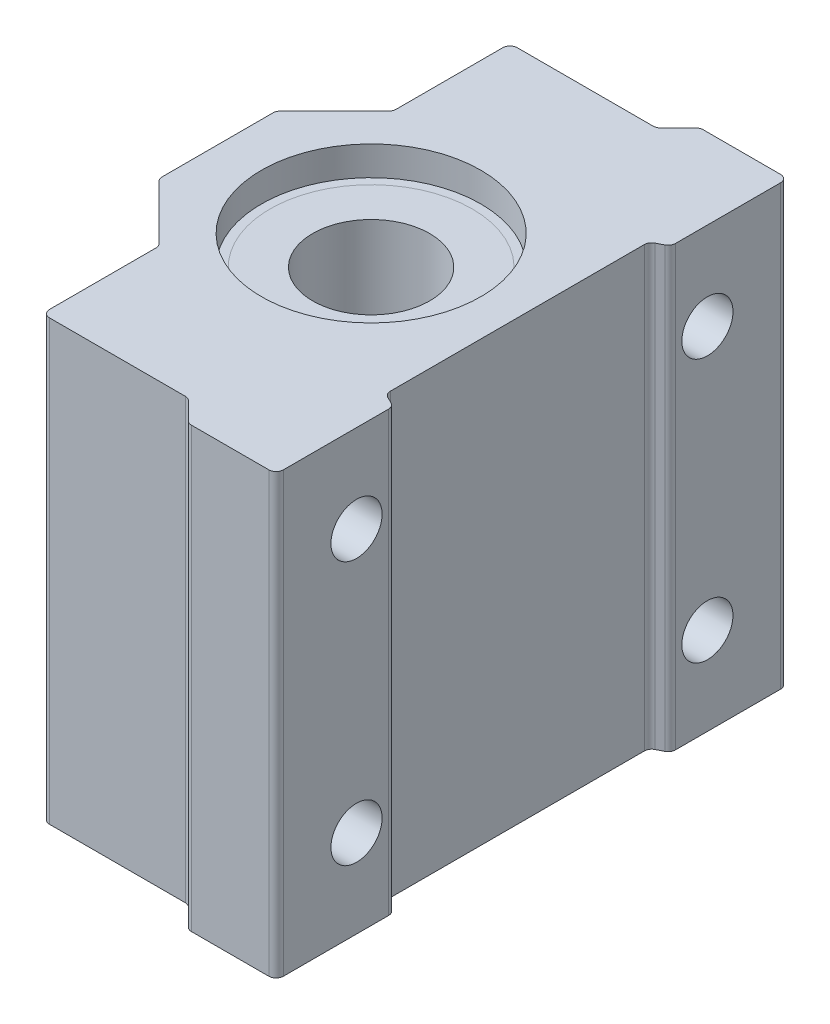
SolidWorks part; units mm, degrees
ref_plane "Front Plane" through (0, 0, 0) normal (0, 0, 1) x (1, 0, 0)
ref_plane "Top Plane" through (0, 0, 0) normal (0, 1, 0) x (1, 0, 0)
ref_plane "Right Plane" through (0, 0, 0) normal (1, 0, 0) x (0, 0, -1)
sketch "Sketch1" plane through (0, 0, 0) normal (0, 1, 0) x (1, 0, 0)
  line L0 (-2.4565, 16.1957) -> (3.5435, 16.1957)
  line L1 (-2.4565, 16.1957) -> (-2.4565, 14.6957) construction
  line L2 (-2.4565, 14.6957) -> (-3.9565, 14.6957) construction
  line L3 (-3.9565, 14.6957) -> (-2.4565, 16.1957)
  line L4 (-3.9565, 14.6957) -> (-13.9565, 14.6957)
  line L5 (-13.9565, 14.6957) -> (-13.9565, 6.6957)
  line L6 (-13.9565, 6.6957) -> (-17.9565, 6.6957) construction
  line L7 (-17.9565, 6.6957) -> (-17.9565, 2.6957) construction
  line L8 (-13.9565, 6.6957) -> (-17.9565, 2.6957)
  line L9 (-17.9565, 2.6957) -> (-17.9565, -5.3043)
  line L10 (-17.9565, -5.3043) -> (-17.9565, -9.3043) construction
  line L11 (-17.9565, -9.3043) -> (-13.9565, -9.3043) construction
  line L12 (-17.9565, -5.3043) -> (-13.9565, -9.3043)
  line L13 (-13.9565, -9.3043) -> (-13.9565, -17.3043)
  line L14 (-13.9565, -17.3043) -> (-3.9565, -17.3043)
  line L15 (-3.9565, -17.3043) -> (-3.9565, -18.8043)
  line L16 (-3.9565, -18.8043) -> (-2.4565, -18.8043) construction
  line L17 (-3.9565, -17.3043) -> (-2.4565, -18.8043)
  line L18 (-2.4565, -18.8043) -> (3.5435, -18.8043)
  line L19 (3.5435, -18.8043) -> (3.5435, -10.8043)
  line L20 (3.5435, 16.1957) -> (3.5435, 8.1957)
  line L21 (3.5435, -10.8043) -> (2.5435, -10.8043) construction
  line L22 (2.5435, -10.8043) -> (2.5435, -10.3043) construction
  line L23 (3.5435, 8.1957) -> (2.5435, 8.1957) construction
  line L24 (2.5435, 8.1957) -> (2.5435, 7.6957) construction
  line L25 (2.5435, -10.3043) -> (3.5435, -10.8043)
  line L26 (2.5435, 7.6957) -> (3.5435, 8.1957)
  line L27 (2.5435, 7.6957) -> (2.5435, -10.3043)
  dimension "D1" = 10
  dimension "D2" = 6
  dimension "D3" = 8
  dimension "D4" = 18
  dimension "D5" = 8
  dimension "D6" = 6
  dimension "D7" = 10
  dimension "D8" = 8
  dimension "D9" = 8
  dimension "D10" = 8
  dimension "D11" = 1.5
  dimension "D12" = 1.5
  dimension "D13" = 1.5
  dimension "D14" = 1.5
  dimension "D15" = 1
  dimension "D16" = 0.5
extrude "Boss-Extrude1" add sketch "Sketch1" along normal blind 30 contours L27 L26 L20 L0 L3 L4 L5 L8 L9 L12 L13 L14 L17 L18 L19 L25 region at (-6.1077, 0, 1.3043)
fillet "Fillet1" radius 0.5 16 edges at (-13.9565, 15, 17.3043) (-3.9565, 15, 17.3043) (-2.4565, 15, 18.8043) (3.5435, 15, 18.8043) (3.5435, 15, 10.8043) (2.5435, 15, 10.3043) (2.5435, 15, -7.6957) (3.5435, 15, -8.1957) (3.5435, 15, -16.1957) (-2.4565, 15, -16.1957) (-3.9565, 15, -14.6957) (-13.9565, 15, -14.6957) (-13.9565, 15, -6.6957) (-17.9565, 15, -2.6957) (-17.9565, 15, 5.3043) (-13.9565, 15, 9.3043)
sketch "Sketch2" plane through (0, 0, 0) normal (0, -1, 0) x (1, 0, 0)
  line L0 (3.5435, -10.612) -> (-7.4565, -10.612) construction
  line L1 (3.5435, -15.6957) -> (3.5435, -8.5047) construction
  line L3 (-7.4565, -14.6957) -> (-7.4565, 1.3043) construction
  line L4 (-4.1636, -14.6957) -> (-13.4565, -14.6957) construction
  circle A0 centre (-7.4565, 1.3043) radius 7.5
  dimension "D3" = 15
  dimension "D1" = 11
  dimension "D2" = 16
extrude "Cut-Extrude1" cut sketch "Sketch2" against normal blind 30
ref_plane "Plane1" through (0, 2, 0) normal (0, 1, 0) x (1, 0, 0)
sketch "Sketch4" plane through (0, 2, 0) normal (0, 1, 0) x (1, 0, 0)
  circle A0 centre (-7.4565, -1.3043) radius 7.5
  circle A1 centre (-7.4565, -1.3043) radius 6.9114
extrude "Boss-Extrude2" add sketch "Sketch4" along normal blind 26
sketch "Sketch5" plane through (0, 2, 0) normal (0, 1, 0) x (1, 0, 0)
  circle A0 centre (-7.4565, -1.3043) radius 6.9114
  circle A1 centre (-7.4565, -1.3043) radius 4
  dimension "D1" = 8
extrude "Boss-Extrude3" add sketch "Sketch5" along normal blind 26 separate body
sketch "Sketch6" plane through (-13.9565, 0, 0) normal (-1, 0, 0) x (0, 0, 1)
  line L0 (1.3043, 30) -> (1.3043, 0) construction
  line L2 (18.6579, 15) -> (-16.0492, 15) construction
  line L5 (18.6579, 0) -> (18.6579, 30) construction
  line L6 (-10.6957, 24) -> (13.3043, 24) construction
  line L7 (-10.6957, 24) -> (-10.6957, 6) construction
  line L8 (-10.6957, 6) -> (13.3043, 6) construction
  line L9 (13.3043, 24) -> (13.3043, 6) construction
  line L10 (-10.6957, 24) -> (13.3043, 6) construction
  line L11 (-10.6957, 6) -> (13.3043, 24) construction
  line L12 (-16.0492, 30) -> (-16.0492, 0) construction
  line L13 (-2.4885, 30) -> (5.0972, 30) construction
  line L14 (-2.4885, 0) -> (5.0972, 0) construction
  circle A0 centre (13.3043, 24) radius 1.75
  circle A1 centre (13.3043, 6) radius 1.75
  circle A2 centre (-10.6957, 6) radius 1.75
  circle A3 centre (-10.6957, 24) radius 1.75
  point P11 (1.3043, 15)
  dimension "D3" = 3.5
  dimension "D4" = 3.5
  dimension "D5" = 3.5
  dimension "D6" = 3.5
  dimension "D1" = 18
  dimension "D2" = 24
extrude "Cut-Extrude2" cut sketch "Sketch6" against normal blind 26
